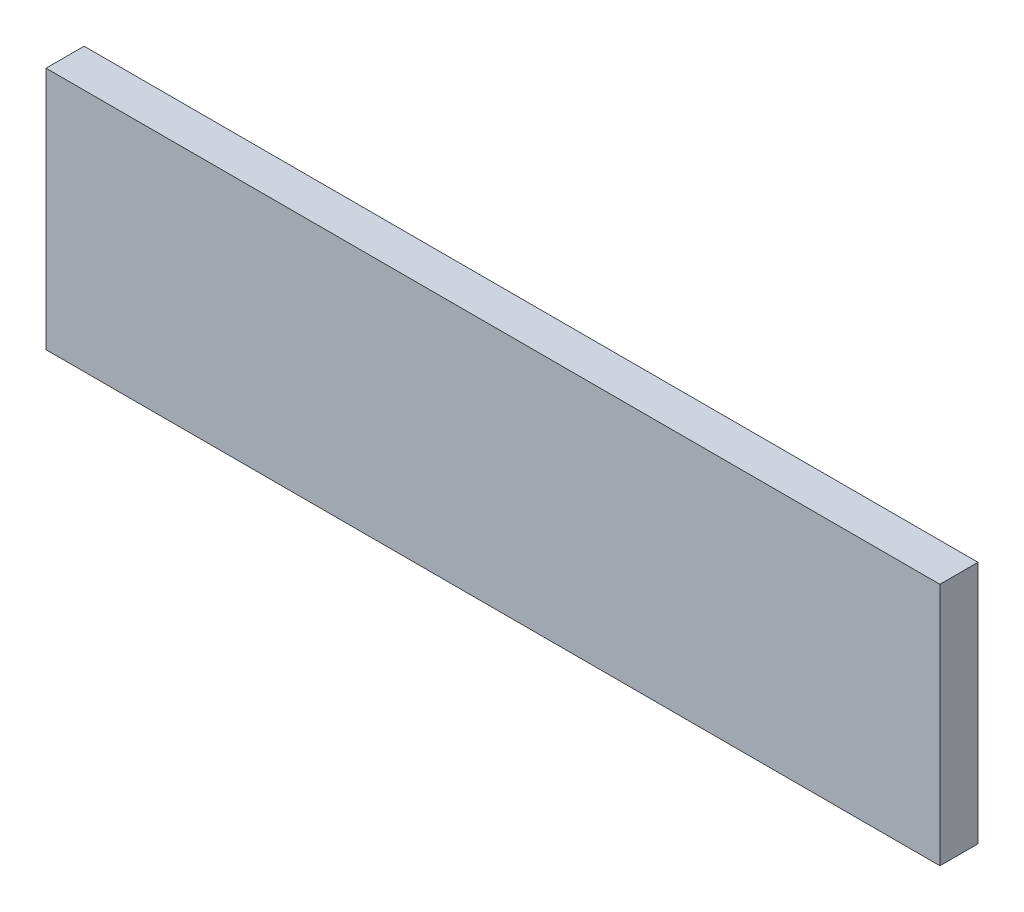
SolidWorks part; units mm, degrees
material "Pine"
ref_plane "Front Plane" through (0, 0, 0) normal (0, 0, 1) x (1, 0, 0)
ref_plane "Top Plane" through (0, 0, 0) normal (0, 1, 0) x (1, 0, 0)
ref_plane "Right Plane" through (0, 0, 0) normal (1, 0, 0) x (0, 0, -1)
sketch "Sketch1" plane through (0, 0, 0) normal (0, 0, 1) x (1, 0, 0)
  line L1 (-61.2395, 49.53) -> (218.1605, 49.53)
  line L2 (-61.2395, 49.53) -> (-61.2395, -26.67)
  line L3 (-61.2395, -26.67) -> (218.1605, -26.67)
  line L4 (218.1605, 49.53) -> (218.1605, -26.67)
  dimension "D1" = 279.4
  dimension "D2" = 76.2
extrude "Boss-Extrude1" add sketch "Sketch1" along normal blind 11.9062
